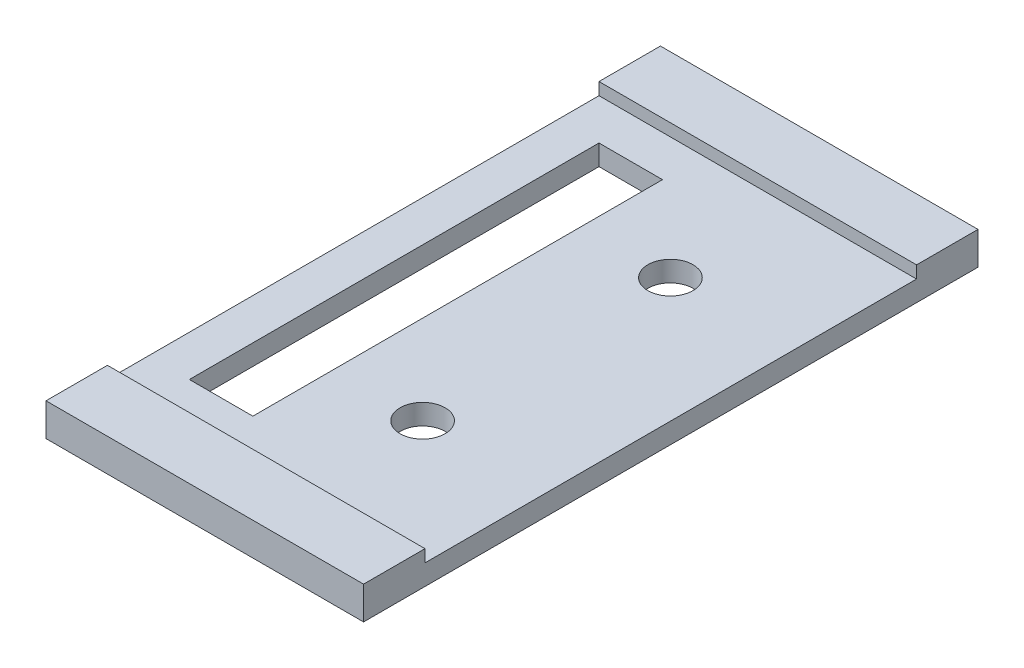
SolidWorks part; units mm, degrees
ref_plane "Front Plane" through (0, 0, 0) normal (0, 0, 1) x (1, 0, 0)
ref_plane "Top Plane" through (0, 0, 0) normal (0, 1, 0) x (1, 0, 0)
ref_plane "Right Plane" through (0, 0, 0) normal (1, 0, 0) x (0, 0, -1)
sketch "Sketch2" plane through (0, 0, 0) normal (0, 1, 0) x (1, 0, 0)
  line L0 (0, 38.1) -> (39.3827, 38.1) construction
  line L1 (0, 0) -> (39.3827, 0)
  line L2 (0, 0) -> (0, 76.2)
  line L3 (0, 76.2) -> (39.3827, 76.2)
  line L4 (39.3827, 0) -> (39.3827, 76.2)
  line L5 (23.9719, 38.1) -> (23.9719, 53.467) construction
  line L6 (23.9719, 38.1) -> (23.9719, 22.733) construction
  line L7 (39.3827, 68.58) -> (0, 68.58)
  line L8 (12.954, 38.1) -> (12.954, 63.5)
  line L9 (12.954, 63.5) -> (5.08, 63.5)
  line L10 (5.08, 63.5) -> (5.08, 12.7)
  line L11 (5.08, 12.7) -> (12.954, 12.7)
  line L12 (12.954, 12.7) -> (12.954, 38.1)
  line L13 (33.1404, 76.2) -> (33.1404, 68.58) construction
  line L14 (28.6413, 0) -> (28.6413, 7.62) construction
  line L15 (39.3827, 7.62) -> (0, 7.62)
  circle A0 centre (23.9719, 53.467) radius 2.794
  circle A1 centre (23.9719, 22.733) radius 2.794
  dimension "D1" = 5.08
  dimension "D2" = 11.0179
  dimension "D3" = 39.3827
extrude "Boss-Extrude2" add sketch "Sketch2" along normal blind 4.064 contours L4 L15 L2 L1 | L7 L4 L3 L2 region at (19.6913, 0, -3.81) region at (19.6913, 0, -72.39)
extrude "Boss-Extrude3" add sketch "Sketch2<3>" along normal blind 2.54 contours L15 L4 L7 L2 A1 A0 L12 L11 L10 L9 L8 region at (21.7714, 0, -38.1)
sketch "Sketch2<3>" plane through (0, 0, 0) normal (0, 1, 0) x (1, 0, 0) same geometry as "Sketch2"
